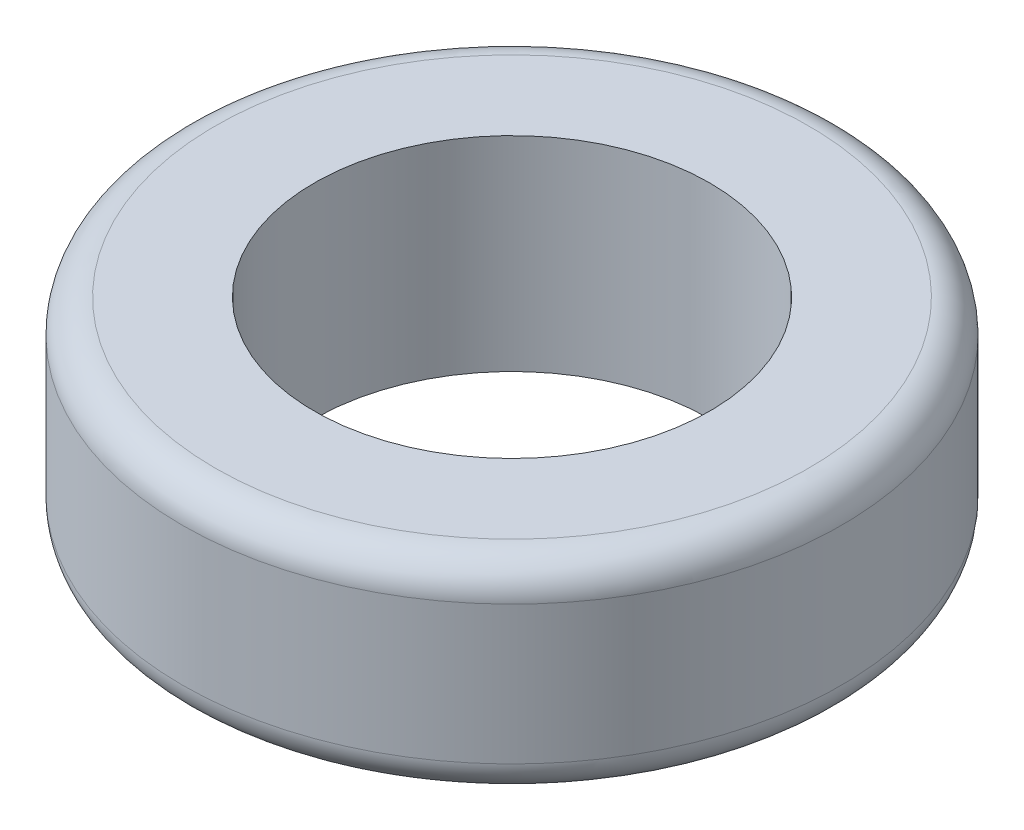
SolidWorks part; units mm, degrees
ref_plane "Front Plane" through (0, 0, 0) normal (0, 0, 1) x (1, 0, 0)
ref_plane "Top Plane" through (0, 0, 0) normal (0, 1, 0) x (1, 0, 0)
ref_plane "Right Plane" through (0, 0, 0) normal (1, 0, 0) x (0, 0, -1)
ref_axis "X-Axis" through (88.99, 0, 0) along (-1, 0, 0)
ref_axis "Y-Axis" through (0, 0, -88.99) along (0, 0, 1)
ref_axis "Z-Axis" through (0, -55, 0) along (0, 1, 0)
sketch "Sketch1" plane through (0, 0, 0) normal (0, 1, 0) x (1, 0, 0)
  circle A0 centre (0, 0) radius 6
  circle A1 centre (0, 0) radius 10
  dimension "D1" = 12
  dimension "D2" = 4
extrude "Boss-Extrude1" add sketch "Sketch1" along normal blind 6.2
fillet "Fillet1" radius 1 2 edges at (0, 0, 10) (0, 6.2, 10)
